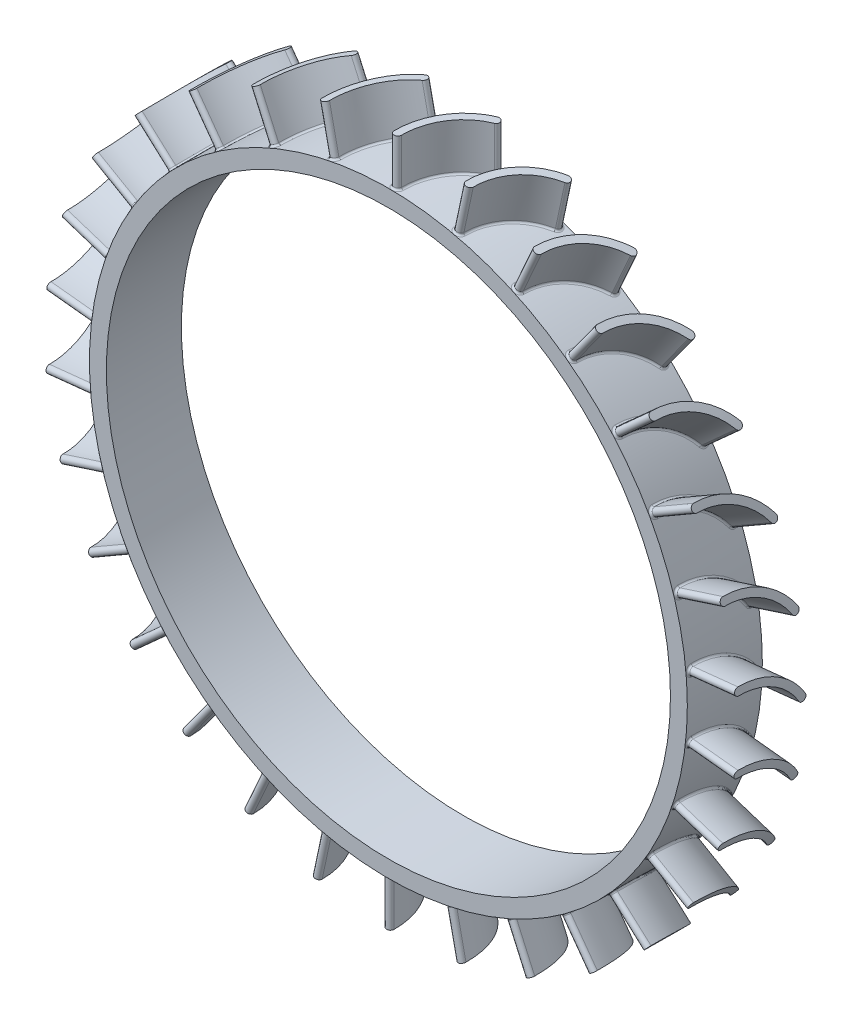
SolidWorks part; units mm, degrees
ref_plane "Front Plane" through (0, 0, 0) normal (0, 0, 1) x (1, 0, 0)
ref_plane "Top Plane" through (0, 0, 0) normal (0, 1, 0) x (1, 0, 0)
ref_plane "Right Plane" through (0, 0, 0) normal (1, 0, 0) x (0, 0, -1)
sketch "Sketch1" plane through (0, 0, 0) normal (0, 0, 1) x (1, 0, 0)
  circle A0 centre (0, 0) radius 75.19
  circle A1 centre (0, 0) radius 79.69
  dimension "D1" = 159.38
  dimension "D2" = 150.38
extrude "Boss-Extrude1" add sketch "Sketch1" along normal mid plane 20
sketch "Sketch2" plane through (0, 0, 0) normal (0, 1, 0) x (1, 0, 0)
  line L0 (-79.69, -10) -> (79.69, -10) construction
  line L1 (79.69, 10) -> (-79.69, 10) construction
  arc A0 (-0.0106, -8.5) -> (10, 9) centre (19.9887, -8.327) cw
  arc A1 (1.9893, -8.4827) -> (10.9989, 7.2673) centre (19.9887, -8.327) cw
  arc A2 (10, 9) -> (10.9989, 7.2673) centre (10.4994, 8.1336) cw
  arc A3 (-0.0106, -8.5) -> (1.9893, -8.4827) centre (0.9894, -8.4914) ccw
  dimension "D4" = 20
  dimension "D1" = 1.5
  dimension "D2" = 1
  dimension "D3" = 10
  dimension "D5" = 2
extrude "Boss-Extrude2" add sketch "Sketch2" along normal offset from surface (14.646 mm away) 17 from offset 77
fillet "Fillet1" radius 0.5 4 edges at (0.8842, 79.6851, 9.4858) (3.2181, 79.625, -2.5702) (9.602, 79.1094, -7.6925) (2.9985, 79.6336, 2.3829)
pattern_circular "CirPattern1" count 30 over 360 about axis through (0, 0, 10) along (0, 0, 1) of "Boss-Extrude2", "Fillet1"
